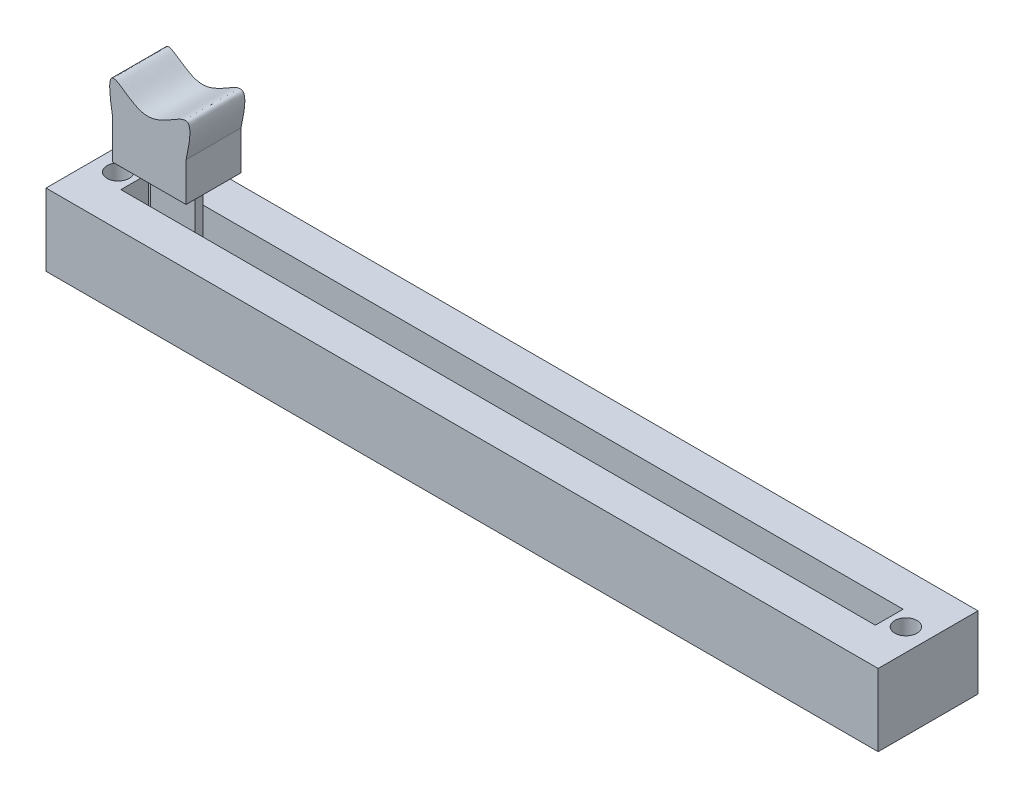
SolidWorks part; units mm, degrees
ref_plane "Front Plane" through (0, 0, 0) normal (0, 0, 1) x (1, 0, 0)
ref_plane "Top Plane" through (0, 0, 0) normal (0, 1, 0) x (1, 0, 0)
ref_plane "Right Plane" through (0, 0, 0) normal (1, 0, 0) x (0, 0, -1)
sketch "Sketch1" plane through (0, 0, 0) normal (0, 1, 0) x (1, 0, 0)
  line L1 (-37.5, -4.5) -> (37.5, -4.5)
  line L2 (-37.5, -4.5) -> (-37.5, 4.5)
  line L3 (-37.5, 4.5) -> (37.5, 4.5)
  line L4 (37.5, -4.5) -> (37.5, 4.5)
  line L5 (-37.5, -4.5) -> (37.5, 4.5) construction
  line L6 (-37.5, 4.5) -> (37.5, -4.5) construction
  line L7 (34, -1.25) -> (-34, -1.25)
  line L8 (34, -1.25) -> (34, 1.25)
  line L9 (34, 1.25) -> (-34, 1.25)
  line L10 (-34, -1.25) -> (-34, 1.25)
  line L11 (34, -1.25) -> (-34, 1.25) construction
  line L12 (34, 1.25) -> (-34, -1.25) construction
  circle A0 centre (-35.5, 0) radius 1
  circle A1 centre (35.5, 0) radius 1
  point P0 (0, 0)
  point P10 (0, 0)
  dimension "D3" = 2
  dimension "D4" = 2
  dimension "D1" = 75
  dimension "D2" = 9
  dimension "D5" = 35.5
  dimension "D6" = 35.5
  dimension "D7" = 4.5
  dimension "D8" = 4.5
  dimension "D9" = 68
  dimension "D10" = 2.5
extrude "Boss-Extrude1" add sketch "Sketch1" along normal blind 6.5 contours L10 L7 L8 L9 | L1 L4 L3 L2 A1 A0 L7 L10 L9 L8 region at (-36.7446, 0, 0) region at (0, 0, 0)
extrude "Cut-Extrude1" cut sketch "Sketch1<3>" along normal blind 6.5 from offset 2 contours L7 L10 L9 L8
sketch "Sketch1<3>" plane through (0, 0, 0) normal (0, 1, 0) x (1, 0, 0) same geometry as "Sketch1"
sketch "Sketch2" plane through (0, 2, 0) normal (0, 1, 0) x (1, 0, 0)
  line L1 (-32.2101, -0.3677) -> (-28.2101, -0.3677)
  line L2 (-32.2101, -0.3677) -> (-32.2101, 0.3677)
  line L3 (-32.2101, 0.3677) -> (-28.2101, 0.3677)
  line L4 (-28.2101, -0.3677) -> (-28.2101, 0.3677)
  line L5 (-32.2101, -0.3677) -> (-28.2101, 0.3677) construction
  line L6 (-32.2101, 0.3677) -> (-28.2101, -0.3677) construction
  point P0 (-30.2101, 0)
  dimension "D1" = 4
extrude "Boss-Extrude2" add sketch "Sketch2" along normal blind 10.5 separate body
sketch "Sketch3" plane through (0, 12.5, 0) normal (0, 1, 0) x (1, 0, 0)
  line L1 (-32.2101, 0.3677) -> (-28.2101, 0.3677)
  line L2 (-32.2101, 0.3677) -> (-32.2101, -0.3677)
  line L3 (-32.2101, -0.3677) -> (-28.2101, -0.3677)
  line L4 (-28.2101, 0.3677) -> (-28.2101, -0.3677)
  line L5 (-33.5208, -2.4743) -> (-26.8995, -2.4743)
  line L6 (-33.5208, -2.4743) -> (-33.5208, 2.4743)
  line L7 (-33.5208, 2.4743) -> (-26.8995, 2.4743)
  line L8 (-26.8995, -2.4743) -> (-26.8995, 2.4743)
  line L9 (-33.5208, -2.4743) -> (-26.8995, 2.4743) construction
  line L10 (-33.5208, 2.4743) -> (-26.8995, -2.4743) construction
  point P6 (-30.2101, 0)
  line M1 (-28.2101, -0.3677) -> (-28.2101, 0.3677)
  line M2 (-28.2101, 0.3677) -> (-32.2101, 0.3677)
  line M3 (-32.2101, 0.3677) -> (-32.2101, -0.3677)
  line M4 (-32.2101, -0.3677) -> (-28.2101, -0.3677)
extrude "Boss-Extrude3" add sketch "Sketch3" along normal blind 0.5 and the other way blind 3 separate body contours L5 L8 L7 L6 M1 M4 M3 M2 | L1 L4 L3 L2 region at (-33.4381, 12.5, 0)
sketch "Sketch5" plane through (0, 0, 2.4743) normal (0, 0, 1) x (1, 0, 0)
  line L0 (-33.5208, 13) -> (-26.8995, 13) construction
  line L1 (-33.5208, 9.5) -> (-33.5208, 13) construction
  line L6 (-26.8995, 9.5) -> (-26.8995, 13)
  line L7 (-26.8995, 13) -> (-33.5208, 13)
  line L8 (-33.5208, 13) -> (-33.5208, 9.5)
  line L9 (-33.5208, 9.5) -> (-26.8995, 9.5)
  line L10 (-26.8995, 9.5) -> (-26.8995, 13)
  line L12 (-33.5208, 13) -> (-33.5208, 9.5)
  line L13 (-33.5208, 9.5) -> (-26.8995, 9.5)
  spline S0 degree 3 poles (-33.5208, 13) (-34.4964, 18.6414) (-30.5232, 10.611) (-25.6043, 18.7746) (-26.8995, 13) knots 0 0 0 0 0.473615 1 1 1 1
  dimension "D1" = 3.0023
  dimension "D2" = 3
  dimension "D3" = 6
  dimension "D4" = 3
  dimension "D5" = 0
extrude "Boss-Extrude4" add sketch "Sketch5" against normal up to surface (4.9485 mm away) up to face at (-30.2101, 11.25, -2.4743)
